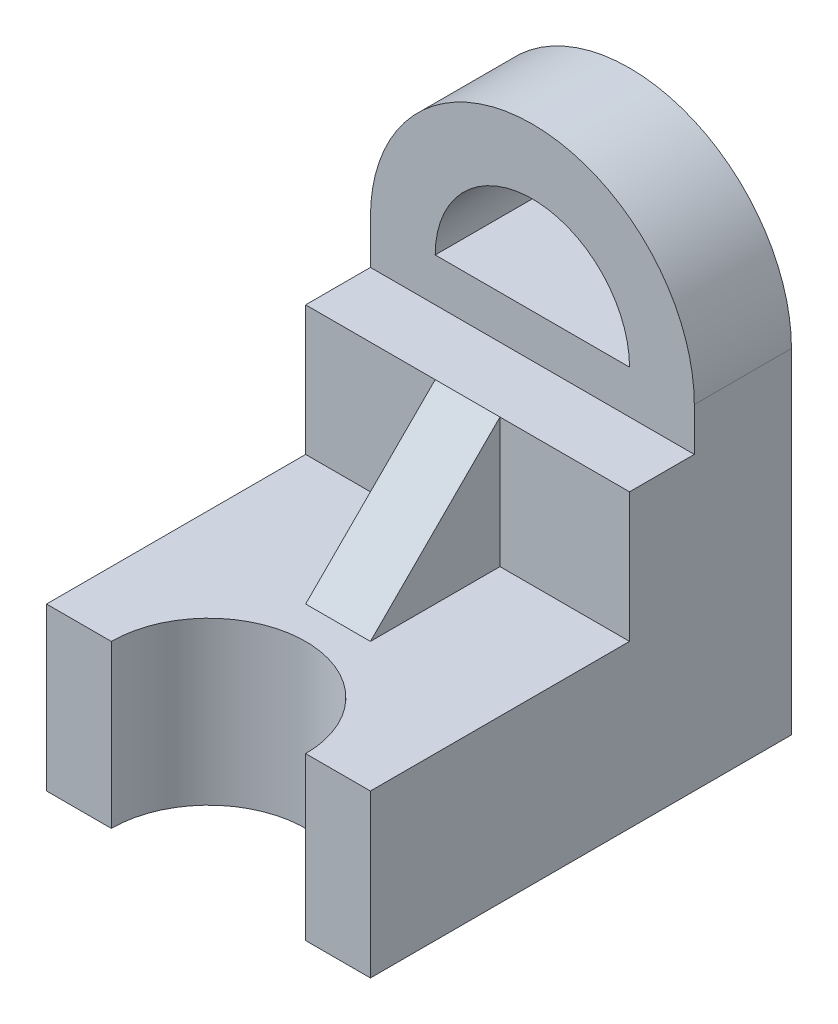
SolidWorks part; units mm, degrees
ref_plane "Front Plane" through (0, 0, 0) normal (0, 0, 1) x (1, 0, 0)
ref_plane "Top Plane" through (0, 0, 0) normal (0, 1, 0) x (1, 0, 0)
ref_plane "Right Plane" through (0, 0, 0) normal (1, 0, 0) x (0, 0, -1)
sketch "Sketch1" plane through (0, 0, 0) normal (0, 0, 1) x (1, 0, 0)
  line L0 (0, 0) -> (0, 73906.17) construction
  line L1 (0, 0) -> (-73906.17, 0) construction
  line L2 (-45, 81) -> (-45, 93)
  line L3 (-45, 0) -> (45, 0)
  line L4 (-45, 0) -> (-45, 45)
  line L5 (-45, 45) -> (45, 45)
  line L6 (45, 0) -> (45, 45)
  line L7 (-45, 45) -> (45, 45)
  line L8 (-45, 45) -> (-45, 81)
  line L9 (-45, 81) -> (45, 81)
  line L10 (45, 45) -> (45, 81)
  line L11 (45, 93) -> (45, 81)
  line L12 (-27, 93) -> (27, 93)
  arc A0 (-45, 93) -> (45, 93) centre (0, 93) cw
  arc A1 (-27, 93) -> (27, 93) centre (0, 93) cw
  point P18 (0, 93)
  dimension "D3" = 12
  dimension "D5" = 27
  dimension "D1" = 45
  dimension "D2" = 36
  dimension "D4" = 90
extrude "Boss-Extrude1" add sketch "Sketch1" along normal blind 117 contours L3 L6 L5 L4 region at (0, 22.5, 0)
extrude "Boss-Extrude2" add sketch "Sketch1<3>" along normal blind 45 contours L5 L10 L9 L8 region at (0, 63, 0)
sketch "Sketch1<3>" plane through (0, 0, 0) normal (0, 0, 1) x (1, 0, 0) same geometry as "Sketch1"
extrude "Boss-Extrude3" add sketch "Sketch1<4>" along normal blind 27 contours A0 L2 L9 L11 L12 A1 region at (-43.9347, 87, 0)
sketch "Sketch1<4>" plane through (0, 0, 0) normal (0, 0, 1) x (1, 0, 0) same geometry as "Sketch1"
sketch "Sketch2" plane through (0, 0, 0) normal (1, 0, 0) x (0, 0, -1)
  line L0 (-45, 81) -> (-81, 45)
  line L1 (-117, 45) -> (-45, 45) construction
  line L2 (-45, 45) -> (-45, 81) construction
  dimension "D1" = 36
rib "Rib2" sketch "Sketch2" sketch "Sketch2" thickness 18 extrusion direction parallel to sketch draft on no parameters "D1"=18
sketch "Sketch3" plane through (0, 45, 0) normal (0, 1, 0) x (1, 0, 0)
  line L0 (-45, -117) -> (45, -117) construction
  circle A0 centre (0, -117) radius 27
  dimension "D1" = 54
extrude "Cut-Extrude1" cut sketch "Sketch3" against normal up to next
